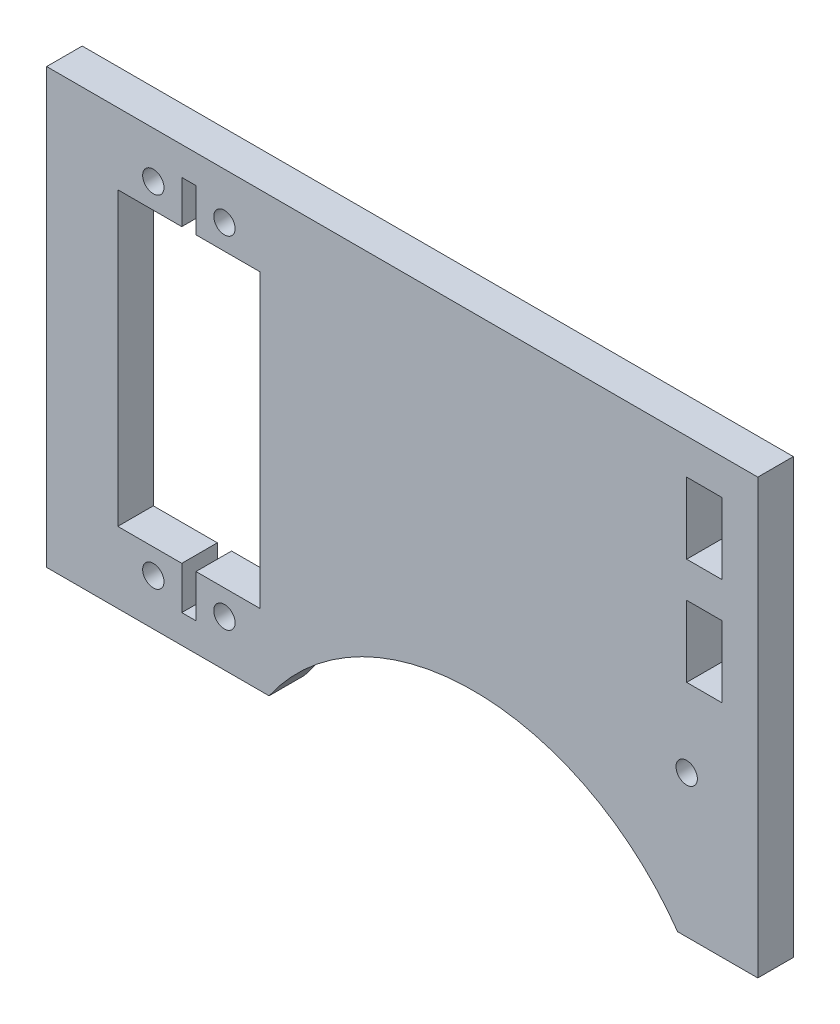
SolidWorks part; units mm, degrees
ref_plane "Plan de face" through (0, 0, 0) normal (0, 0, 1) x (1, 0, 0)
ref_plane "Plan de dessus" through (0, 0, 0) normal (0, 1, 0) x (1, 0, 0)
ref_plane "Plan de droite" through (0, 0, 0) normal (1, 0, 0) x (0, 0, -1)
sketch "Esquisse1" plane through (0, 0, 0) normal (0, 0, 1) x (1, 0, 0)
  line L0 (20, 71) -> (20, 0) construction
  line L1 (0, 0) -> (31.2772, 0)
  line L2 (0, 0) -> (0, 61)
  line L3 (0, 61) -> (100, 61)
  line L4 (100, 0) -> (100, 61)
  line L5 (10, 30.5) -> (30, 30.5) construction
  line L6 (10, 51) -> (19, 51)
  line L7 (10, 51) -> (10, 10)
  line L8 (10, 10) -> (19, 10)
  line L9 (30, 51) -> (30, 10)
  line L10 (20, 20) -> (90, 20) construction
  line L11 (88.7228, 0) -> (100, 0)
  line L12 (21, 4) -> (21, 10)
  line L13 (19, 57) -> (21, 57)
  line L14 (19, 57) -> (19, 51)
  line L15 (21, 10) -> (30, 10)
  line L16 (21, 57) -> (21, 51)
  line L17 (19, 4) -> (21, 4)
  line L18 (19, 4) -> (19, 10)
  line L19 (21, 51) -> (30, 51)
  line L21 (90, 56) -> (95, 56)
  line L22 (90, 56) -> (90, 46)
  line L23 (90, 46) -> (95, 46)
  line L24 (95, 56) -> (95, 46)
  line L25 (90, 41) -> (95, 41)
  line L26 (90, 41) -> (90, 31)
  line L27 (90, 31) -> (95, 31)
  line L28 (95, 41) -> (95, 31)
  circle A0 centre (15, 6.5) radius 1.5
  circle A1 centre (25, 6.5) radius 1.5
  circle A2 centre (25, 54.5) radius 1.5
  circle A3 centre (15, 54.5) radius 1.5
  circle A4 centre (20, 20) radius 1.5 construction
  circle A5 centre (20, 20) radius 1.5 construction
  circle A6 centre (90, 20) radius 1.5
  circle A7 centre (60, -20) radius 35 construction
  arc A8 (31.2772, 0) -> (88.7228, 0) centre (60, -20) cw
  dimension "D6" = 3.5
  dimension "D8" = 3
  dimension "D9" = 3
  dimension "D10" = 70
  dimension "D13" = 70
  dimension "D16" = 2
  dimension "D1" = 10
  dimension "D2" = 41
  dimension "D3" = 20
  dimension "D4" = 10
  dimension "D5" = 100
  dimension "D7" = 5
  dimension "D11" = 10
  dimension "D12" = 10
  dimension "D14" = 40
  dimension "D15" = 40
  dimension "D17" = 6
  dimension "D18" = 5
  dimension "D19" = 5
  dimension "D20" = 10
  dimension "D21" = 5
  dimension "D22" = 5
extrude "Boss.-Extru.1" add sketch "Esquisse1" along normal blind 5
